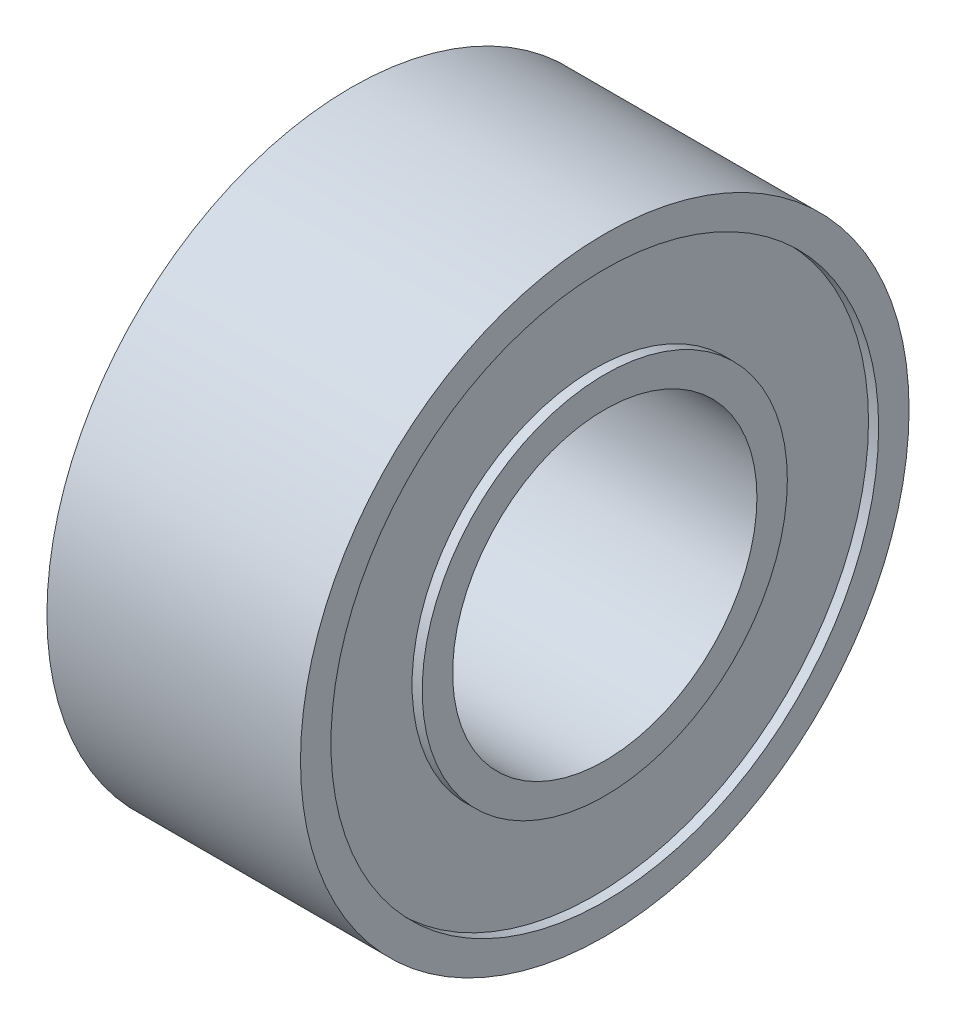
SolidWorks part; units mm, degrees
ref_plane "Plan de face" through (0, 0, 0) normal (0, 0, 1) x (1, 0, 0)
ref_plane "Plan de dessus" through (0, 0, 0) normal (0, 1, 0) x (1, 0, 0)
ref_plane "Plan de droite" through (0, 0, 0) normal (1, 0, 0) x (0, 0, -1)
sketch "Esquisse1" plane through (0, 0, 0) normal (1, 0, 0) x (0, 0, -1)
  circle A0 centre (0, 0) radius 3
  circle A1 centre (0, 0) radius 1.5
  circle A2 centre (0, 0) radius 2.7
  circle A3 centre (0, 0) radius 1.8
  dimension "D1" = 6
  dimension "D2" = 3
  dimension "D3" = 0.3
  dimension "D4" = 0.3
extrude "Boss.-Extru.1" add sketch "Esquisse1" along normal mid plane 2.5 contours A0 A1 | A3 A1 region at (0, 0, 2.9151) region at (0, 0, 1.7491)
sketch "Esquisse2" plane through (0, 0, 0) normal (1, 0, 0) x (0, 0, -1)
  circle A1 centre (0, 0) radius 1.8
  circle A2 centre (0, 0) radius 1.8 construction
  circle A4 centre (0, 0) radius 2.7 construction
  circle A5 centre (0, 0) radius 2.7
extrude "Boss.-Extru.2" add sketch "Esquisse2" along normal mid plane 2.3
ref_axis "Axe1" through (1.25, 0, 0) along (-1, 0, 0)
equation "\"D4@Esquisse1\"=\"D3@Esquisse1\""
